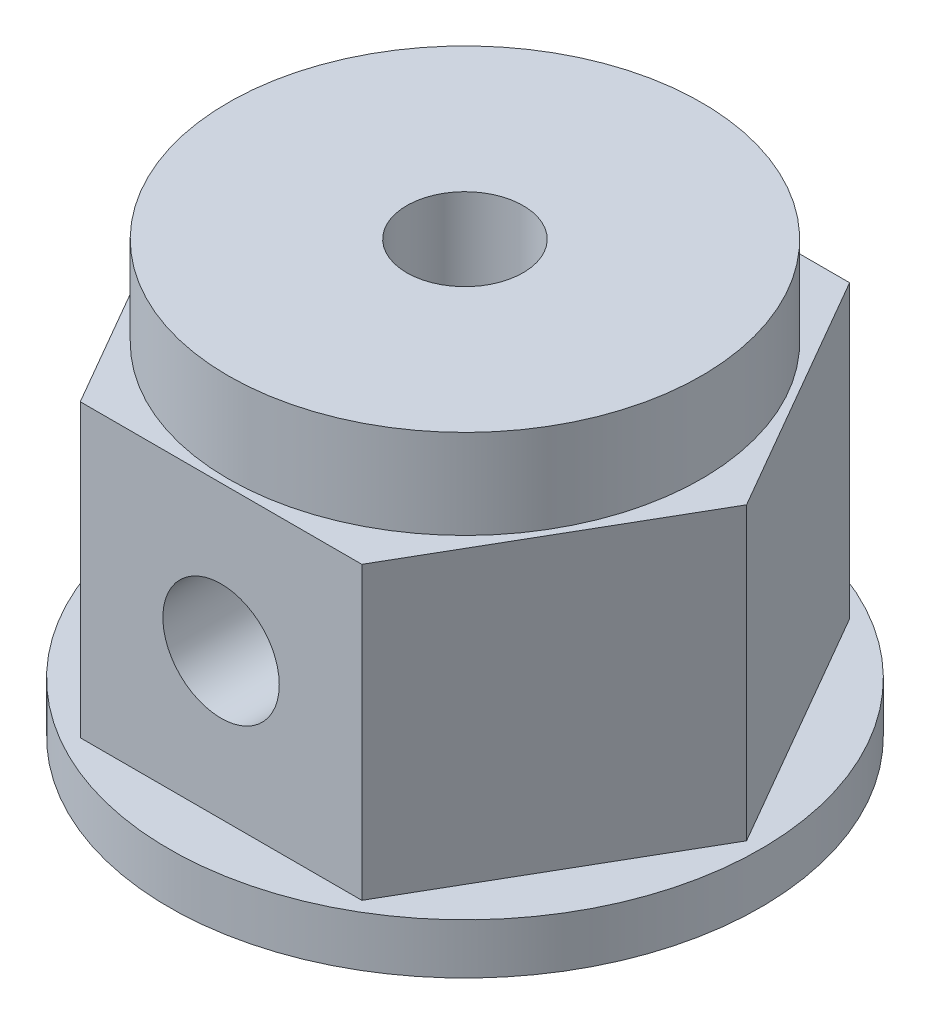
SolidWorks part; units mm, degrees
ref_plane "Front Plane" through (0, 0, 0) normal (0, 0, 1) x (1, 0, 0)
ref_plane "Top Plane" through (0, 0, 0) normal (0, 1, 0) x (1, 0, 0)
ref_plane "Right Plane" through (0, 0, 0) normal (1, 0, 0) x (0, 0, -1)
sketch "Sketch1" plane through (0, 0, 0) normal (0, 1, 0) x (1, 0, 0)
  line L1 (7.2573, 0) -> (3.6286, 6.285)
  line L2 (3.6286, 6.285) -> (-3.6286, 6.285)
  line L3 (-3.6286, 6.285) -> (-7.2573, 0)
  line L4 (-7.2573, 0) -> (-3.6286, -6.285)
  line L5 (-3.6286, -6.285) -> (3.6286, -6.285)
  line L6 (3.6286, -6.285) -> (7.2573, 0)
  circle A0 centre (0, 0) radius 6.285 construction
  dimension "D1" = 12.57
extrude "Boss-Extrude1" add sketch "Sketch1" along normal blind 7.5
sketch "Sketch2" plane through (0, 7.5, 0) normal (0, 1, 0) x (1, 0, 0)
  circle A0 centre (0, 0) radius 6.1
  dimension "D1" = 12.2
extrude "Boss-Extrude2" add sketch "Sketch2" along normal blind 2.3
sketch "Sketch3" plane through (0, 0, 0) normal (0, -1, 0) x (1, 0, 0)
  circle A0 centre (0, 0) radius 7.625
  dimension "D1" = 15.25
extrude "Boss-Extrude3" add sketch "Sketch3" along normal blind 1.3
sketch "Sketch4" plane through (0, 9.8, 0) normal (0, 1, 0) x (1, 0, 0)
  circle A0 centre (0, 0) radius 1.5
  dimension "D1" = 3
extrude "Cut-Extrude1" cut sketch "Sketch4" against normal through all
sketch "Sketch5" plane through (0, 0, 6.285) normal (0, 0, 1) x (1, 0, 0)
  circle A0 centre (0, 3.75) radius 1.5
  dimension "D1" = 3
  dimension "D2" = 3.75
extrude "Cut-Extrude2" cut sketch "Sketch5" against normal up to next
